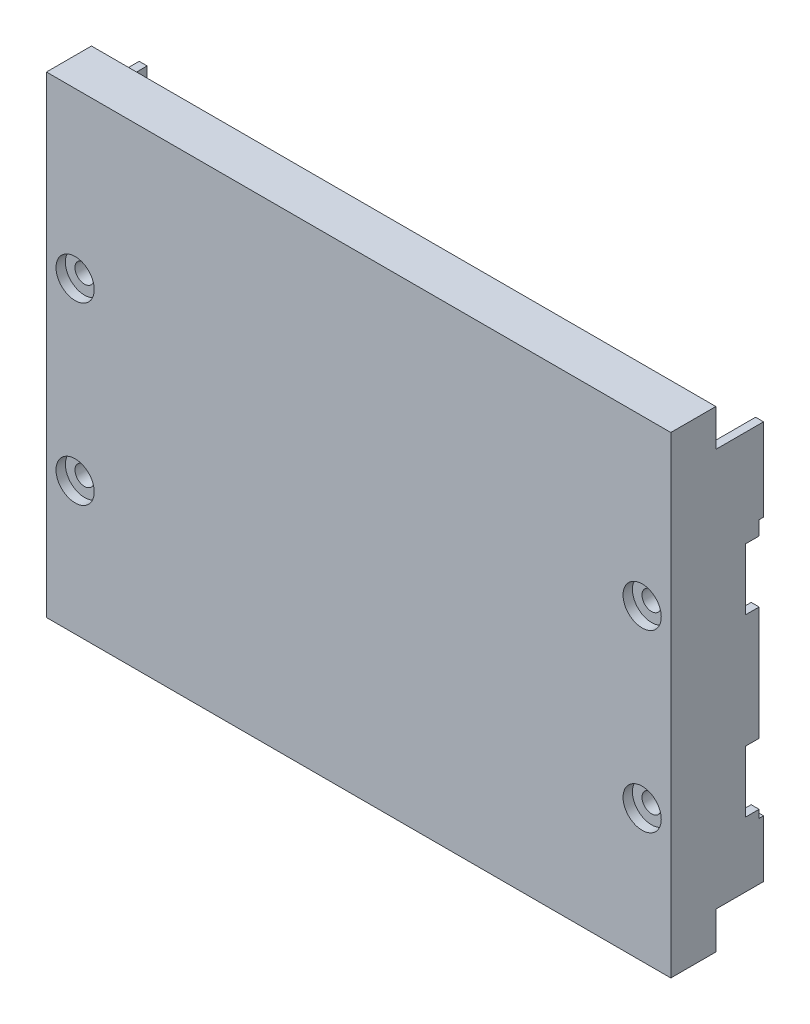
SolidWorks part; units mm, degrees
ref_plane "Front Plane" through (0, 0, 0) normal (0, 0, 1) x (1, 0, 0)
ref_plane "Top Plane" through (0, 0, 0) normal (0, 1, 0) x (1, 0, 0)
ref_plane "Right Plane" through (0, 0, 0) normal (1, 0, 0) x (0, 0, -1)
sketch "Sketch1" plane through (0, 0, 0) normal (0, 0, 1) x (1, 0, 0)
  line L0 (-30.5002, 35.0258) -> (66.0198, 35.0258) construction
  line L1 (67.5438, 35.0258) -> (-32.0242, 35.0258)
  line L2 (67.5438, 35.0258) -> (67.5438, -28.4742)
  line L3 (67.5438, -28.4742) -> (-32.0242, -28.4742)
  line L4 (-32.0242, 35.0258) -> (-32.0242, -28.4742)
  line L5 (66.0198, -28.4742) -> (-30.5002, -28.4742) construction
  line L7 (66.0198, 35.0258) -> (66.0198, -28.4742) construction
  line L8 (-30.5002, -28.4742) -> (-30.5002, 35.0258) construction
  dimension "D1" = 1.524
  dimension "D2" = 1.524
extrude "base" add sketch "Sketch1" along normal blind 5.08
sketch "Sketch2" plane through (0, 0, 0) normal (0, 0, -1) x (-1, 0, 0)
  line L0 (-67.5438, 35.0258) -> (32.0242, 35.0258) construction
  line L1 (30.5002, -26.9502) -> (-66.0198, -26.9502)
  line L2 (30.5002, -26.9502) -> (30.5002, 33.5018)
  line L3 (30.5002, 33.5018) -> (-66.0198, 33.5018)
  line L4 (-66.0198, -26.9502) -> (-66.0198, 33.5018)
  line L5 (-67.5438, -28.4742) -> (-67.5438, 35.0258) construction
  line L6 (32.0242, -28.4742) -> (-67.5438, -28.4742) construction
  line L7 (32.0242, 35.0258) -> (32.0242, -28.4742) construction
  dimension "D1" = 1.524
  dimension "D2" = 1.524
  dimension "D3" = 1.524
  dimension "D4" = 1.524
extrude "hollow" cut sketch "Sketch2" against normal blind 2
sketch "Sketch3" plane through (0, 0, 0) normal (0, 0, -1) x (-1, 0, 0)
  line L0 (-67.5438, 35.0258) -> (32.0242, 35.0258) construction
  line L1 (30.7542, 35.0258) -> (32.0242, 35.0258)
  line L2 (30.7542, 35.0258) -> (30.7542, -28.4742)
  line L3 (30.7542, -28.4742) -> (32.0242, -28.4742)
  line L4 (32.0242, 35.0258) -> (32.0242, -28.4742)
  line L5 (32.0242, -28.4742) -> (-67.5438, -28.4742) construction
  line L7 (32.0242, 35.0258) -> (32.0242, -28.4742) construction
  line L9 (-67.5438, 35.0258) -> (-66.2738, 35.0258)
  line L10 (-67.5438, 35.0258) -> (-67.5438, -28.4742)
  line L11 (-67.5438, -28.4742) -> (-66.2738, -28.4742)
  line L12 (-66.2738, 35.0258) -> (-66.2738, -28.4742)
  dimension "D1" = 1.27
  dimension "D2" = 1.27
extrude "end pieces" add sketch "Sketch3" along normal blind 9
sketch "Sketch7" plane through (67.5438, 0, 0) normal (1, 0, 0) x (0, 0, -1)
  line L0 (9, 35.0258) -> (9, -28.4742) construction
  line L1 (6.7986, 9.8068) -> (9, 9.8068)
  line L2 (6.7986, 9.8068) -> (6.7986, 19.6048)
  line L3 (6.7986, 19.6048) -> (9, 19.6048)
  line L4 (9, 9.8068) -> (9, 19.6048)
  line L5 (6.9986, 19.4048) -> (16.7986, 19.4048) construction
  line L6 (6.9986, 19.4048) -> (6.9986, 10.0068) construction
  line L7 (6.9986, 10.0068) -> (16.7986, 10.0068) construction
  line L8 (6.9986, -17.9332) -> (16.7986, -17.9332) construction
  line L9 (6.7986, -18.1332) -> (9, -18.1332)
  line L10 (6.7986, -18.1332) -> (6.7986, -8.3352)
  line L11 (6.7986, -8.3352) -> (9, -8.3352)
  line L12 (9, -18.1332) -> (9, -8.3352)
  dimension "D1" = 0.2
  dimension "D2" = 0.2
  dimension "D3" = 0.2
  dimension "D4" = 0.2
extrude "where top intrudes" cut sketch "Sketch7" against normal through all
sketch "cable stop wings alt" plane through (0, 0, 5.08) normal (0, 0, 1) x (1, 0, 0)
  line L1 (-32.0242, -28.4742) -> (67.5438, -28.4742)
  line L2 (-32.0242, -28.4742) -> (-32.0242, -33.4742)
  line L3 (-32.0242, -33.4742) -> (67.5438, -33.4742)
  line L4 (67.5438, -28.4742) -> (67.5438, -33.4742)
  line L5 (67.5438, 35.0258) -> (-32.0242, 35.0258) construction
  line L6 (-32.0242, -28.4742) -> (67.5438, -28.4742) construction
  line L8 (-32.0242, 35.0258) -> (67.5438, 35.0258)
  line L9 (-32.0242, 35.0258) -> (-32.0242, 40.0258)
  line L10 (-32.0242, 40.0258) -> (67.5438, 40.0258)
  line L11 (67.5438, 35.0258) -> (67.5438, 40.0258)
  line L12 (67.5438, -28.4742) -> (67.5438, 35.0258) construction
  line L13 (-32.0242, 35.0258) -> (-32.0242, -28.4742) construction
  dimension "D1" = 5
extrude "cable stop wing boss alt" add sketch "cable stop wings alt" against normal blind 1.5
sketch "Sketch4" plane through (0, 0, 2) normal (0, 0, -1) x (-1, 0, 0)
  circle A0 centre (-62.9718, 14.7058) radius 2.794
  circle A1 centre (-62.9718, -13.2342) radius 2.794
  circle A2 centre (27.4522, -13.2342) radius 2.794
  circle A4 centre (27.4522, 14.7058) radius 2.794
extrude "screw bosses" add sketch "Sketch4" along normal up to surface (2 mm away) up to face at (17.7598, 3.2758, 0)
sketch "Sketch5" plane through (0, 0, 0) normal (0, 0, -1) x (-1, 0, 0)
  circle A0 centre (-62.9718, 14.7058) radius 1.524
  circle A1 centre (-62.9718, -13.2342) radius 1.524
  circle A2 centre (27.4522, 14.7058) radius 1.524
  circle A3 centre (27.4522, -13.2342) radius 1.524
extrude "screw holes" cut sketch "Sketch5" against normal through all
sketch "Sketch6" plane through (0, 0, 5.08) normal (0, 0, 1) x (1, 0, 0)
  circle A0 centre (62.9718, -13.2342) radius 3.048
  circle A1 centre (62.9718, 14.7058) radius 3.048
  circle A2 centre (-27.4522, -13.2342) radius 3.048
  circle A4 centre (-27.4522, 14.7058) radius 3.048
extrude "counter sink" cut sketch "Sketch6" against normal blind 1.5
sketch "Sketch14" plane through (0, 0, 5.08) normal (0, 0, 1) x (1, 0, 0)
  line L5 (35.9798, 34.9458) -> (65.9798, 34.9458) construction
  line L6 (59.8698, 34.9458) -> (42.0898, 34.9458)
  line L7 (59.8698, 34.9458) -> (59.8698, 40.0258)
  line L8 (59.8698, 40.0258) -> (42.0898, 40.0258)
  line L9 (42.0898, 34.9458) -> (42.0898, 40.0258)
  line L10 (59.8698, 34.9458) -> (42.0898, 40.0258) construction
  line L11 (59.8698, 40.0258) -> (42.0898, 34.9458) construction
  line L12 (33.5728, 34.9458) -> (3.5728, 34.9458) construction
  line L13 (1.4638, 34.9458) -> (-28.5362, 34.9458) construction
  line L15 (-22.4262, 40.0258) -> (-4.6462, 40.0258)
  line L16 (-22.4262, 40.0258) -> (-22.4262, 34.9458)
  line L17 (-22.4262, 34.9458) -> (-4.6462, 34.9458)
  line L18 (-4.6462, 40.0258) -> (-4.6462, 34.9458)
  line L19 (-22.4262, 40.0258) -> (-4.6462, 34.9458) construction
  line L20 (-22.4262, 34.9458) -> (-4.6462, 40.0258) construction
  line L21 (9.6828, 34.9458) -> (27.4628, 34.9458)
  line L22 (9.6828, 34.9458) -> (9.6828, 40.0258)
  line L23 (9.6828, 40.0258) -> (27.4628, 40.0258)
  line L24 (27.4628, 34.9458) -> (27.4628, 40.0258)
  line L25 (9.6828, 34.9458) -> (27.4628, 40.0258) construction
  line L26 (9.6828, 40.0258) -> (27.4628, 34.9458) construction
  line L27 (67.5438, 40.0258) -> (-32.0242, 40.0258) construction
  point P0 (50.9798, 37.4858)
  point P7 (50.9798, 34.9458)
  point P18 (-13.5362, 37.4858)
  point P23 (18.5728, 37.4858)
  point P28 (18.5728, 34.9458)
  point P29 (-13.5362, 34.9458)
  dimension "D1" = 17.78
  dimension "D2" = 5.08
sketch "Sketch15" plane through (0, 0, 5.08) normal (0, 0, -1) x (-1, 0, 0)
  line L0 (-65.5698, -28.3942) -> (-35.5698, -28.3942) construction
  line L1 (-59.4598, -28.3942) -> (-41.6798, -28.3942)
  line L2 (-59.4598, -28.3942) -> (-59.4598, -33.4742)
  line L3 (-59.4598, -33.4742) -> (-41.6798, -33.4742)
  line L4 (-41.6798, -28.3942) -> (-41.6798, -33.4742)
  line L5 (-59.4598, -28.3942) -> (-41.6798, -33.4742) construction
  line L6 (-59.4598, -33.4742) -> (-41.6798, -28.3942) construction
  line L7 (-27.0528, -28.3942) -> (-9.2728, -28.3942)
  line L8 (-27.0528, -28.3942) -> (-27.0528, -33.4742)
  line L9 (-27.0528, -33.4742) -> (-9.2728, -33.4742)
  line L10 (-9.2728, -28.3942) -> (-9.2728, -33.4742)
  line L11 (-27.0528, -28.3942) -> (-9.2728, -33.4742) construction
  line L12 (-27.0528, -33.4742) -> (-9.2728, -28.3942) construction
  line L13 (5.3572, -28.3942) -> (23.1372, -28.3942)
  line L14 (5.3572, -28.3942) -> (5.3572, -33.4742)
  line L15 (5.3572, -33.4742) -> (23.1372, -33.4742)
  line L16 (23.1372, -28.3942) -> (23.1372, -33.4742)
  line L17 (5.3572, -28.3942) -> (23.1372, -33.4742) construction
  line L18 (5.3572, -33.4742) -> (23.1372, -28.3942) construction
  line L19 (-33.1628, -28.3942) -> (-3.1628, -28.3942) construction
  line L20 (-0.7528, -28.3942) -> (29.2472, -28.3942) construction
  line L21 (32.0242, -33.4742) -> (-67.5438, -33.4742) construction
  point P0 (-50.5698, -30.9342)
  point P5 (-18.1628, -30.9342)
  point P10 (14.2472, -30.9342)
  point P19 (-50.5698, -28.3942)
  point P24 (-18.1628, -28.3942)
  point P29 (14.2472, -28.3942)
  dimension "D1" = 5.08
  dimension "D2" = 17.78
sketch "Sketch25" plane through (0, 0, 5.08) normal (0, 0, 1) x (1, 0, 0)
  line L0 (-105.8162, 35.9458) -> (-135.1786, 35.9458) construction
  line L1 (-32.0242, 40.9458) -> (67.5438, 40.9458)
  line L2 (-32.0242, 40.9458) -> (-32.0242, 36.4458)
  line L3 (-32.0242, 36.4458) -> (67.5438, 36.4458)
  line L4 (67.5438, 40.9458) -> (67.5438, 36.4458)
  line L7 (67.5438, -34.3942) -> (-32.0242, -34.3942)
  line L8 (67.5438, -34.3942) -> (67.5438, -29.8942)
  line L9 (67.5438, -29.8942) -> (-32.0242, -29.8942)
  line L10 (-32.0242, -34.3942) -> (-32.0242, -29.8942)
  line L13 (-32.0242, 40.0258) -> (-32.0242, -33.4742) construction
  line L14 (67.5438, -33.4742) -> (67.5438, 40.0258) construction
  line L15 (-135.5901, -29.3942) -> (-106.2277, -29.3942) construction
  dimension "D1" = 0.5
  dimension "D2" = 5
  dimension "D3" = 0.5
  dimension "D4" = 5
extrude "box under connectors" add sketch "Sketch25" against normal offset from surface (7.1786 mm away) 3.81
sketch "Sketch26" plane through (-32.0242, 0, 0) normal (-1, 0, 0) x (0, 0, 1)
  line L0 (-2.0986, 40.9458) -> (5.08, 40.9458) construction
  line L1 (-2.0986, -34.3942) -> (5.08, -34.3942)
  line L2 (-2.0986, -34.3942) -> (-2.0986, 40.9458)
  line L3 (-2.0986, 40.9458) -> (5.08, 40.9458)
  line L4 (5.08, -34.3942) -> (5.08, 40.9458)
  line L5 (-2.0986, -34.3942) -> (5.08, -34.3942) construction
extrude "Fill ends" add sketch "Sketch26" against normal blind 1.5
extrude "Fill the other end" add sketch "Sketch26<2>" along normal blind 1.5 from surface starting at face at (67.5438, 2.2598, -3.2554)
sketch "Sketch26<2>" plane through (-32.0242, 0, 0) normal (-1, 0, 0) x (0, 0, 1) same geometry as "Sketch26"
sketch "Sketch27" plane through (-32.0242, 0, 0) normal (-1, 0, 0) x (0, 0, 1)
  line L0 (-10.2086, -28.4742) -> (-10.2086, -18.8862) construction
  line L1 (-9, -28.4742) -> (-9.7086, -28.4742)
  line L2 (-9, -28.4742) -> (-9, -19.3862)
  line L3 (-9, -19.3862) -> (-9.7086, -19.3862)
  line L4 (-9.7086, -28.4742) -> (-9.7086, -19.3862)
  line L5 (-9, -18.8862) -> (-10.2086, -18.8862) construction
  line L6 (-9, 21.3568) -> (-10.2086, 21.3568) construction
  line L7 (-9, 35.0258) -> (-9.7086, 35.0258)
  line L8 (-9, 35.0258) -> (-9, 21.8568)
  line L9 (-9, 21.8568) -> (-9.7086, 21.8568)
  line L10 (-9.7086, 35.0258) -> (-9.7086, 21.8568)
  line L11 (-10.2086, 21.3568) -> (-10.2086, 35.0258) construction
  dimension "D1" = 0.5
  dimension "D2" = 0.5
  dimension "D3" = 0.5
  dimension "D4" = 0.5
extrude "Boss-Extrude4" add sketch "Sketch27" against normal up to vertex (1.27 mm away) up to point (-30.7542, 35.0258, -9)
extrude "Boss-Extrude5" add sketch "Sketch27<2>" along normal up to vertex (-98.298 mm away) from surface up to point (66.2738, 35.0258, -9) starting at face at (67.5438, 2.0058, -4.9643)
sketch "Sketch27<2>" plane through (-32.0242, 0, 0) normal (-1, 0, 0) x (0, 0, 1) same geometry as "Sketch27"
